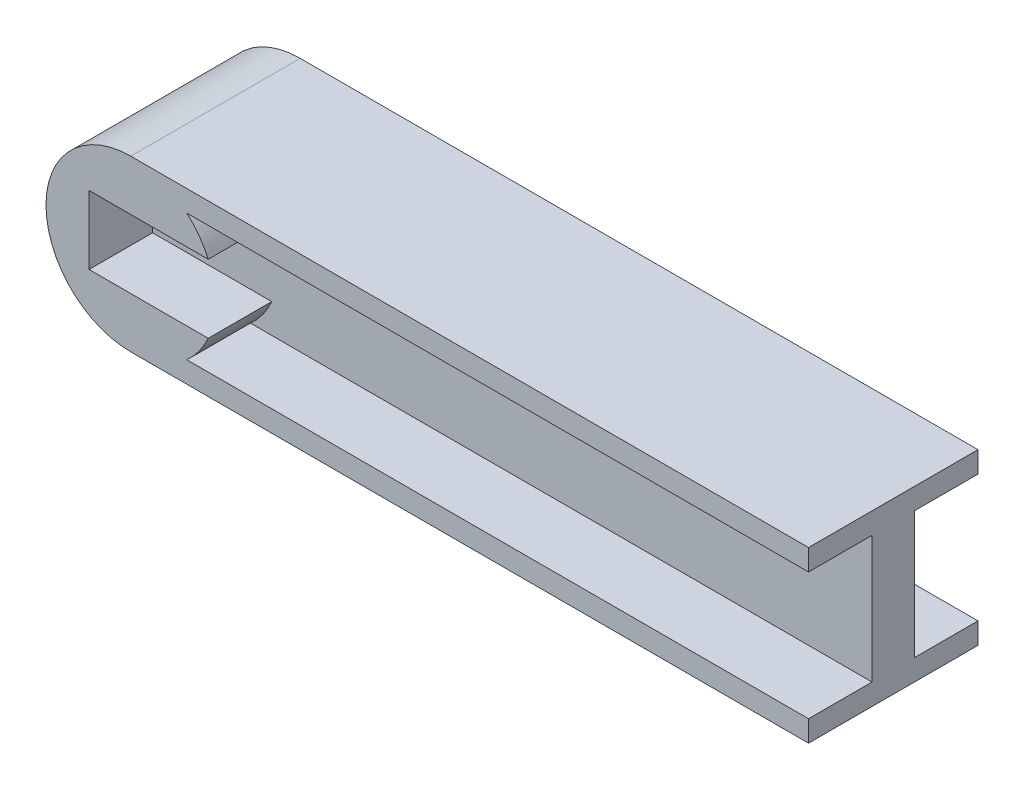
SolidWorks part; units mm, degrees
ref_plane "Front Plane" through (0, 0, 0) normal (0, 0, 1) x (1, 0, 0)
ref_plane "Top Plane" through (0, 0, 0) normal (0, 1, 0) x (1, 0, 0)
ref_plane "Right Plane" through (0, 0, 0) normal (1, 0, 0) x (0, 0, -1)
sketch "Sketch1" plane through (0, 0, 0) normal (0, 1, 0) x (1, 0, 0)
  line L0 (-40, -10) -> (-40, 10)
  line L1 (-40, -10) -> (40, -10)
  line L2 (-40, 10) -> (40, 10)
  line L3 (40, -10) -> (40, 10)
  line L4 (-40, -10) -> (40, 10) construction
  line L5 (-40, 10) -> (40, -10) construction
  point P1 (0, 0)
  dimension "D1" = 80
  dimension "D2" = 20
extrude "Boss-Extrude1" add sketch "Sketch1" along normal mid plane 20
sketch "Sketch2" plane through (0, 0, 0) normal (0, 1, 0) x (1, 0, 0)
  line L0 (40, 10) -> (40, 2.5)
  line L1 (40, -10) -> (-40, -10)
  line L2 (-40, -10) -> (-40, -2.5)
  line L3 (-40, 10) -> (40, 10)
  line L4 (-40, 2.5) -> (40, 2.5)
  line L6 (40, -2.5) -> (-40, -2.5)
  line L8 (0, 2.5) -> (0, -2.5) construction
  line L9 (-40, 2.5) -> (-40, 10)
  line L10 (40, -2.5) -> (40, -10)
  point P14 (0, 0)
  dimension "D1" = 5
extrude "Cut-Extrude1" cut sketch "Sketch2" against normal mid plane 15
sketch "Sketch3" plane through (0, 0, 0) normal (0, 0, 1) x (1, 0, 0)
  line L20 (-40, -7.5) -> (-40, 7.5) construction
  circle A5 centre (-40, 0) radius 10
extrude "Boss-Extrude2" add sketch "Sketch3" along normal mid plane 20
sketch "Sketch8" plane through (0, 0, 10) normal (0, 0, 1) x (1, 0, 0)
  line L1 (-15.082, -4.0393) -> (-44.918, -4.0393)
  line L2 (-15.082, -4.0393) -> (-15.082, 4.0393)
  line L3 (-15.082, 4.0393) -> (-44.918, 4.0393)
  line L4 (-44.918, -4.0393) -> (-44.918, 4.0393)
  line L5 (-15.082, -4.0393) -> (-44.918, 4.0393) construction
  line L6 (-15.082, 4.0393) -> (-44.918, -4.0393) construction
  arc A0 (-33.3856, -7.5) -> (-33.3856, 7.5) centre (-40, 0) ccw construction
  point P0 (-30, 0)
extrude "Cut-Extrude2" cut sketch "Sketch8" against normal up to surface (7.5 mm away) up to face at (4.1536, 0, 2.5)
sketch "Sketch9" plane through (0, 0, -10) normal (0, 0, -1) x (-1, 0, 0)
  circle A0 centre (40, 0) radius 3.8
  dimension "D1" = 7.6
extrude "Cut-Extrude3" cut sketch "Sketch9" against normal blind 5
